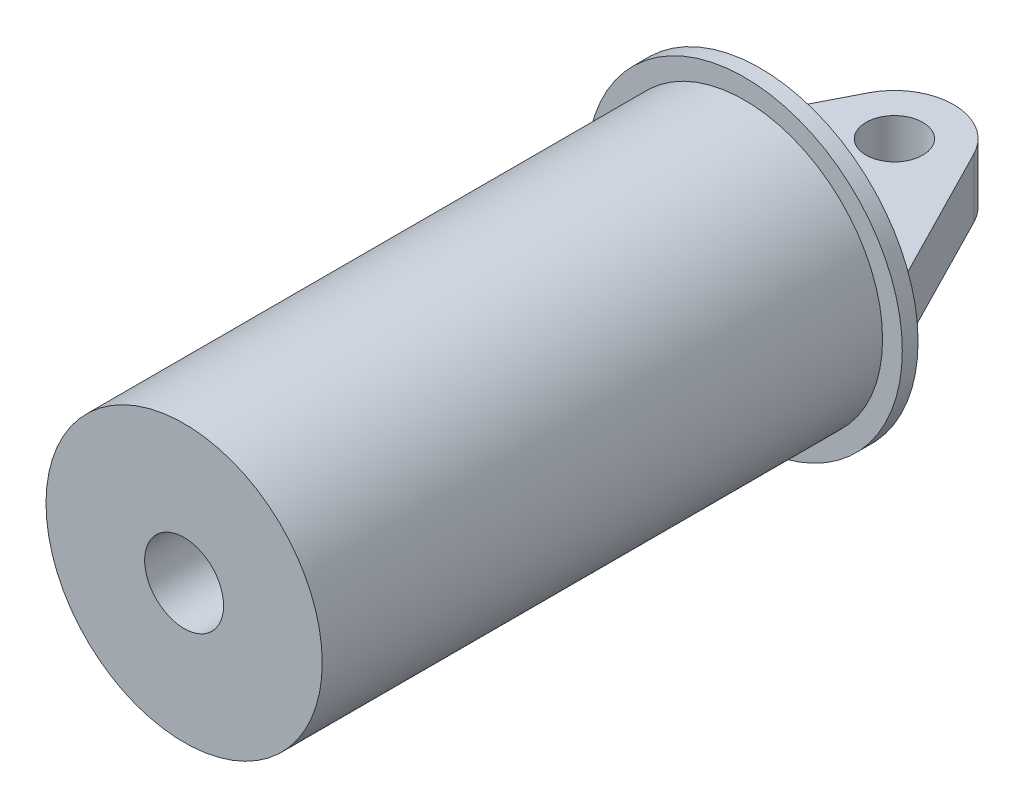
SolidWorks part; units mm, degrees
note: The reader was unsure of these and kept them because the rebuilt part matched: shared geometry of "Sketch1<3>".
material "Plain Carbon Steel"
ref_plane "Front" through (0, 0, 0) normal (0, 0, 1) x (1, 0, 0)
ref_plane "Top" through (0, 0, 0) normal (0, 1, 0) x (1, 0, 0)
ref_plane "Right" through (0, 0, 0) normal (1, 0, 0) x (0, 0, -1)
sketch "Sketch1" plane through (0, 0, 0) normal (0, 0, 1) x (1, 0, 0)
  circle A0 centre (0, 0) radius 12.7
  circle A1 centre (0, 0) radius 11.1125
  circle A2 centre (0, 0) radius 3.175
  dimension "D1" = 25.4
  dimension "D2" = 22.225
  dimension "D3" = 6.35
extrude "Boss-Extrude1" add sketch "Sketch1" along normal blind 2.54 contours A0 A1 | A1 A2 | A2
extrude "Boss-Extrude2" add sketch "Sketch1<3>" along normal blind 47.625 contours A1 A2
sketch "Sketch1<3>" plane through (0, 0, 0) normal (0, 0, 1) x (1, 0, 0) same geometry as "Sketch1"
chamfer "Chamfer1" distance 2.54 distance2 1.27 1 edges at (12.7, 0, 0)
sketch "Sketch2" plane through (0, 0, 0) normal (0, 1, 0) x (1, 0, 0)
  line L0 (-4.2403, 11.6932) -> (-11.1125, -1.7463)
  line L1 (-11.1125, -1.7463) -> (11.1125, -1.7463)
  line L2 (11.1125, -1.7463) -> (4.2403, 11.6932)
  line L3 (-12.7, -2.54) -> (12.7, -2.54) construction
  circle A0 centre (0, 9.525) radius 2.286
  arc A1 (4.2403, 11.6932) -> (-4.2403, 11.6932) centre (0, 9.525) ccw
  point P10 (0, -1.7463)
  dimension "D1" = 4.572
  dimension "D2" = 9.525
  dimension "D3" = 9.525
  dimension "D4" = 0.7937
  dimension "D5" = 22.225
extrude "Boss-Extrude3" add sketch "Sketch2" along normal mid plane 4.7625
fillet "Fillet1" radius 3.175 2 edges
fillet "Fillet2" radius 3.175 2 edges at (0, -2.3813, 0) (0, 2.3813, 0)
